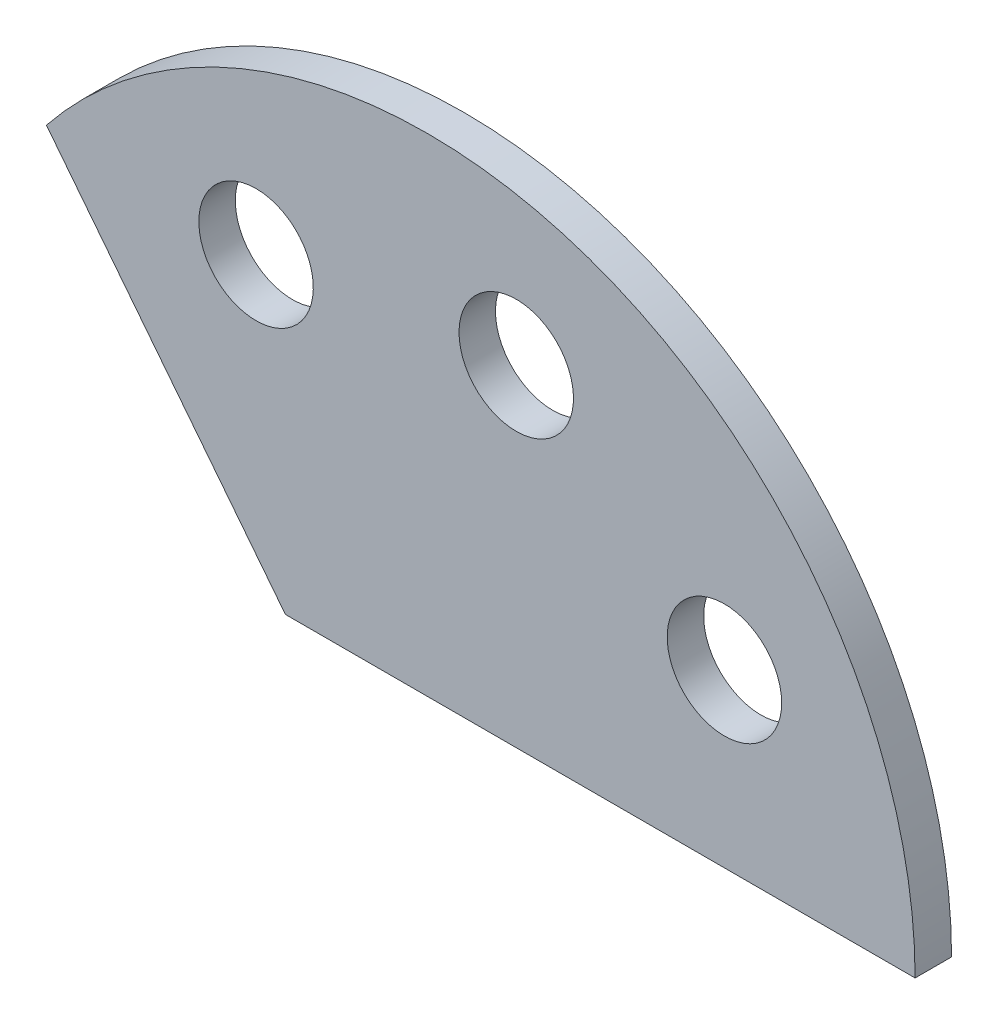
SolidWorks part; units mm, degrees
ref_plane "Front Plane" through (0, 0, 0) normal (0, 0, 1) x (1, 0, 0)
ref_plane "Top Plane" through (0, 0, 0) normal (0, 1, 0) x (1, 0, 0)
ref_plane "Right Plane" through (0, 0, 0) normal (1, 0, 0) x (0, 0, -1)
sketch "Sketch1" plane through (0, 0, 0) normal (0, 0, 1) x (1, 0, 0)
  line L0 (-17.8261, 0) -> (61.1685, 0)
  line L1 (0, 0) -> (37.2483, 21.5053) construction
  line L4 (-47.8025, 38.1642) -> (-17.8261, 0)
  arc A0 (61.1685, 0) -> (-47.8025, 38.1642) centre (0, 0) ccw
  circle A2 centre (37.2483, 21.5053) radius 7.178
  dimension "D1" = 30
extrude "Extrude1" add sketch "Sketch1" against normal blind 4.572
pattern_circular "CirPattern3" count 3 every 45 about axis through (0, 0, -4.572) along (0, 0, 1) of face at (44.4264, 21.5053, -4.572)
